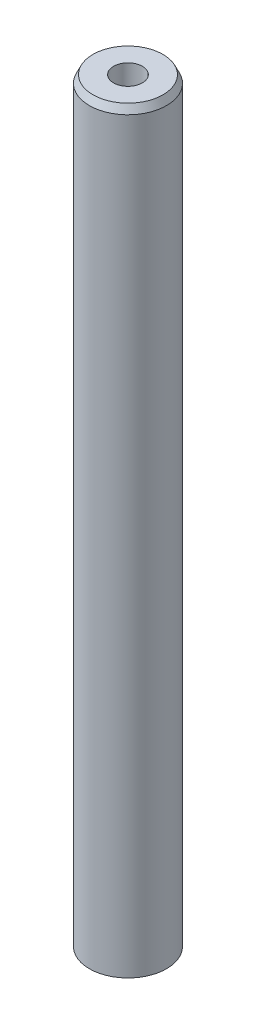
SolidWorks part; units mm, degrees
ref_plane "Front Plane" through (0, 0, 0) normal (0, 0, 1) x (1, 0, 0)
ref_plane "Top Plane" through (0, 0, 0) normal (0, 1, 0) x (1, 0, 0)
ref_plane "Right Plane" through (0, 0, 0) normal (1, 0, 0) x (0, 0, -1)
sketch "Sketch1" plane through (0, 0, 0) normal (0, 1, 0) x (1, 0, 0)
  circle A0 centre (0, 0) radius 5
  dimension "SHAFT_OD" = 10
extrude "Boss-Extrude1" add sketch "Sketch1" along normal blind 98.301
sketch "Sketch2" plane through (0, 0, 0) normal (0, 1, 0) x (1, 0, 0)
  circle A0 centre (0, 0) radius 1.8673
  dimension "BORE_D" = 3.7346
extrude "Cut-Extrude1" cut sketch "Sketch2" along normal through all
chamfer "Chamfer1" distance 0.9782 angle 25.322 2 edges at (0, 98.301, 5) (0, 0, 5) first distance on face at (0, 98.301, 5) first distance on face at (0, 0, 1.8673)
